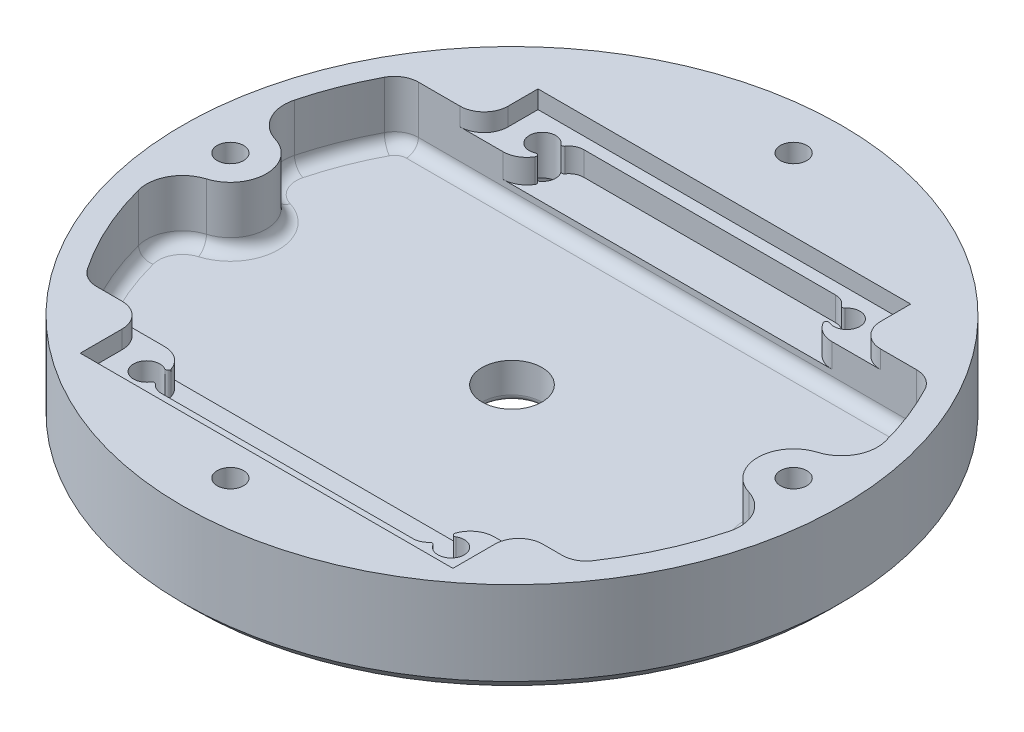
SolidWorks part; units mm, degrees
ref_plane "Спереди" through (0, 0, 0) normal (0, 0, 1) x (1, 0, 0)
ref_plane "Сверху" through (0, 0, 0) normal (0, 1, 0) x (1, 0, 0)
ref_plane "Справа" through (0, 0, 0) normal (1, 0, 0) x (0, 0, -1)
sketch "Эскиз1" plane through (0, 0, 0) normal (0, 1, 0) x (1, 0, 0)
  circle A0 centre (0, 0) radius 27.5
  dimension "D1" = 55
extrude "Бобышка-Вытянуть1" add sketch "Эскиз1" against normal blind 3
sketch "Эскиз2" plane through (0, 0, 0) normal (0, 1, 0) x (1, 0, 0)
  circle A0 centre (0, 0) radius 27.5
  circle A1 centre (0, 0) radius 25.5
  circle A2 centre (0, 0) radius 27.5 construction
  dimension "D1" = 2
extrude "Бобышка-Вытянуть2" add sketch "Эскиз2" along normal blind 5
sketch "Эскиз3" plane through (0, 0, 0) normal (0, 1, 0) x (1, 0, 0)
  line L0 (-21.9552, 12.97) -> (21.9552, 12.97)
  line L1 (15.05, -20.23) -> (-15.05, -20.23) construction
  line L2 (15.05, -20.23) -> (15.05, 16.97) construction
  line L3 (15.05, 16.97) -> (-15.05, 16.97) construction
  line L4 (-15.05, -20.23) -> (-15.05, 16.97) construction
  line L5 (15.05, -20.23) -> (-15.05, 16.97) construction
  line L6 (15.05, 16.97) -> (-15.05, -20.23) construction
  line L7 (-20.4523, -15.23) -> (20.4523, -15.23)
  circle A1 centre (0, 0) radius 25.5
  circle A2 centre (0, 0) radius 25.5 construction
  point P0 (0, -1.63)
  circle M5 centre (0, 0) radius 25.5
  dimension "D1" = 20.23
  dimension "D2" = 37.2
  dimension "D3" = 30.1
  dimension "D4" = 4
  dimension "D5" = 5
extrude "Бобышка-Вытянуть3" add sketch "Эскиз3" along normal up to surface (5 mm away) contours L0 M5 | L7 M5 region at (0, 0, -18.1053) region at (0, 0, 19.4183) up to face at (0, 5, 27.5)
sketch "Эскиз6" plane through (0, 5, 0) normal (0, 1, 0) x (1, 0, 0)
  line L1 (-15.3, 17.47) -> (15.8, 17.47)
  line L2 (-15.3, 17.47) -> (-15.3, -20.73)
  line L3 (-15.3, -20.73) -> (15.8, -20.73)
  line L4 (15.8, 17.47) -> (15.8, -20.73)
  line L5 (-15.3, 17.47) -> (15.8, -20.73) construction
  line L6 (-15.3, -20.73) -> (15.8, 17.47) construction
  point P0 (0.25, -1.63)
  dimension "D1" = 20.73
  dimension "D2" = 31.1
  dimension "D3" = 38.2
  dimension "D4" = 0.25
extrude "Вырез-Вытянуть1" cut sketch "Эскиз6" against normal blind 1.5
sketch "Эскиз7" plane through (0, 3.5, 0) normal (0, 1, 0) x (1, 0, 0)
  line L0 (-10.5, 15.24) -> (10.5, 15.24) construction
  line L1 (-10.5, 16.49) -> (10.5, 16.49)
  line L2 (-10.5, 13.99) -> (10.5, 13.99)
  line L4 (0, 0) -> (0, 15.24) construction
  line L5 (0, 12.97) -> (0, -15.23) construction
  line L6 (0, 17.47) -> (0, 12.97) construction
  line L7 (-20.4523, -15.23) -> (20.4523, -15.23) construction
  line L8 (-10.25, -1.13) -> (10.25, -1.13) construction
  line L9 (-15.3, 12.97) -> (15.8, 12.97) construction
  line L12 (15.8, 17.47) -> (-15.3, 17.47) construction
  line L13 (-11.75, 15.24) -> (-11.75, 12.97)
  line L14 (-21.9552, 12.97) -> (21.9552, 12.97) construction
  line L15 (-11.75, 12.97) -> (11.75, 12.97)
  line L16 (11.75, 12.97) -> (11.75, 15.24)
  line L17 (11.75, -15.23) -> (11.75, -17.5)
  line L18 (-10.5, -17.5) -> (10.5, -17.5) construction
  line L19 (-10.5, -18.75) -> (10.5, -18.75)
  line L20 (-10.5, -16.25) -> (10.5, -16.25)
  line L21 (-11.75, -17.5) -> (-11.75, -15.23)
  line L22 (-11.75, -15.23) -> (11.75, -15.23)
  arc A0 (-10.5, 16.49) -> (-10.5, 13.99) centre (-10.5, 15.24) ccw
  arc A1 (10.5, 13.99) -> (10.5, 16.49) centre (10.5, 15.24) ccw
  arc A2 (-10.5, -18.75) -> (-10.5, -16.25) centre (-10.5, -17.5) cw
  arc A3 (10.5, -16.25) -> (10.5, -18.75) centre (10.5, -17.5) cw
  point P2 (0, 15.24)
  point P13 (0, -1.13)
  point P33 (0, -17.5)
  line M7 (-15.3, 12.97) -> (15.8, 12.97)
  dimension "D1" = 2.5
  dimension "D2" = 23.5
  dimension "D3" = 2.23
extrude "Вырез-Вытянуть2" cut sketch "Эскиз7" against normal blind 2 contours L2 A1 L1 A0 | A1 L2 A0 L13 L16 M7 | L20 A3 L17 L22 L21 A2 | L19 A3 L20 A2 region at (0, 3.5, -15.24) region at (0, 3.5, -13.5015) region at (0, 3.5, 15.7615)
sketch "Эскиз8" plane through (0, 3.5, 0) normal (0, 1, 0) x (1, 0, 0)
  line L0 (0, 0) -> (0, -18.046) construction
  circle A0 centre (-12.7, -17.78) radius 1.1
  circle A1 centre (12.7, -17.78) radius 1.1
  circle A2 centre (-12.7, 15.24) radius 1.1
  circle A3 centre (12.7, 15.24) radius 1.1
  dimension "D3" = 2.2
  dimension "D5" = 2.2
  dimension "D1" = 17.78
  dimension "D2" = 12.7
  dimension "D4" = 15.24
extrude "Вырез-Вытянуть3" cut sketch "Эскиз8" against normal through all
sketch "Эскиз9" plane through (0, 5, 0) normal (0, 1, 0) x (1, 0, 0)
  line L0 (0, 23.5) -> (0, -23.5) construction
  line L1 (-23.5, 3) -> (-25.3229, 3)
  line L2 (-23.5, -3) -> (-25.3229, -3)
  line L3 (23.5, 3) -> (25.3229, 3)
  line L4 (23.5, -3) -> (25.3229, -3)
  circle A0 centre (0, 0) radius 23.5 construction
  arc A1 (-23.5, -3) -> (-23.5, 3) centre (-23.5, 0) ccw
  arc A2 (-21.9552, 12.97) -> (-20.4523, -15.23) centre (0, 0) ccw construction
  arc A3 (-21.9552, 12.97) -> (-20.4523, -15.23) centre (0, 0) ccw construction
  arc A4 (-25.3229, -3) -> (-25.3229, 3) centre (0, 0) cw
  arc A5 (23.5, -3) -> (23.5, 3) centre (23.5, 0) cw
  arc A6 (25.3229, -3) -> (25.3229, 3) centre (0, 0) ccw
  dimension "D1" = 47
  dimension "D2" = 6
extrude "Бобышка-Вытянуть4" add sketch "Эскиз9" against normal through all
sketch "Эскиз10" plane through (0, 5, 0) normal (0, 1, 0) x (1, 0, 0)
  circle A0 centre (0, 0) radius 23.5 construction
  circle A1 centre (0, 23.5) radius 1.1
  circle A2 centre (23.5, 0) radius 1.1
  circle A3 centre (0, -23.5) radius 1.1
  circle A4 centre (-23.5, 0) radius 1.1
  dimension "D1" = 47
  dimension "D2" = 2.2
extrude "Вырез-Вытянуть4" cut sketch "Эскиз10" against normal through all
sketch "Эскиз11" plane through (0, -3, 0) normal (0, -1, 0) x (1, 0, 0)
  line L0 (0, 0) -> (0, 23.5) construction
  line L1 (1.1258, 21.55) -> (2.2517, 23.5) construction
  line L2 (2.2517, 23.5) -> (1.1258, 25.45) construction
  line L3 (1.1258, 25.45) -> (-1.1258, 25.45) construction
  line L4 (-1.1258, 25.45) -> (-2.2517, 23.5) construction
  line L5 (-2.2517, 23.5) -> (-1.1258, 21.55) construction
  line L6 (-1.1258, 21.55) -> (1.1258, 21.55) construction
  line L7 (13.8258, 15.83) -> (14.9517, 17.78)
  line L8 (14.9517, 17.78) -> (13.8258, 19.73)
  line L9 (13.8258, 19.73) -> (11.5742, 19.73)
  line L10 (11.5742, 19.73) -> (10.4483, 17.78)
  line L11 (10.4483, 17.78) -> (11.5742, 15.83)
  line L12 (11.5742, 15.83) -> (13.8258, 15.83)
  line L13 (-11.5742, 15.83) -> (-13.8258, 15.83)
  line L14 (-10.4483, 17.78) -> (-11.5742, 15.83)
  line L15 (-11.5742, 19.73) -> (-10.4483, 17.78)
  line L16 (-13.8258, 19.73) -> (-11.5742, 19.73)
  line L17 (-14.9517, 17.78) -> (-13.8258, 19.73)
  line L18 (-13.8258, 15.83) -> (-14.9517, 17.78)
  line L19 (21.55, -1.1258) -> (23.5, -2.2517) construction
  line L20 (23.5, -2.2517) -> (25.45, -1.1258) construction
  line L21 (25.45, -1.1258) -> (25.45, 1.1258) construction
  line L22 (25.45, 1.1258) -> (23.5, 2.2517) construction
  line L23 (23.5, 2.2517) -> (21.55, 1.1258) construction
  line L24 (21.55, 1.1258) -> (21.55, -1.1258) construction
  line L25 (-1.1258, -21.55) -> (-2.2517, -23.5) construction
  line L26 (-2.2517, -23.5) -> (-1.1258, -25.45) construction
  line L27 (-1.1258, -25.45) -> (1.1258, -25.45) construction
  line L28 (1.1258, -25.45) -> (2.2517, -23.5) construction
  line L29 (2.2517, -23.5) -> (1.1258, -21.55) construction
  line L30 (1.1258, -21.55) -> (-1.1258, -21.55) construction
  line L31 (-21.55, 1.1258) -> (-23.5, 2.2517) construction
  line L32 (-23.5, 2.2517) -> (-25.45, 1.1258) construction
  line L33 (-25.45, 1.1258) -> (-25.45, -1.1258) construction
  line L34 (-25.45, -1.1258) -> (-23.5, -2.2517) construction
  line L35 (-23.5, -2.2517) -> (-21.55, -1.1258) construction
  line L36 (-21.55, -1.1258) -> (-21.55, 1.1258) construction
  line L37 (-12.7, 17.78) -> (-12.7, -15.24) construction
  line L38 (-12.7, 1.27) -> (13.8258, 1.27) construction
  line L39 (11.5742, -13.29) -> (13.8258, -13.29)
  line L40 (10.4483, -15.24) -> (11.5742, -13.29)
  line L41 (11.5742, -17.19) -> (10.4483, -15.24)
  line L42 (13.8258, -17.19) -> (11.5742, -17.19)
  line L43 (14.9517, -15.24) -> (13.8258, -17.19)
  line L44 (13.8258, -13.29) -> (14.9517, -15.24)
  line L45 (-10.4483, -15.24) -> (-11.5742, -13.29)
  line L46 (-11.5742, -17.19) -> (-10.4483, -15.24)
  line L47 (-13.8258, -17.19) -> (-11.5742, -17.19)
  line L48 (-14.9517, -15.24) -> (-13.8258, -17.19)
  line L49 (-13.8258, -13.29) -> (-14.9517, -15.24)
  line L50 (-11.5742, -13.29) -> (-13.8258, -13.29)
  circle A0 centre (0, 23.5) radius 1.95 construction
  circle A1 centre (12.7, 17.78) radius 1.95 construction
  circle A2 centre (-12.7, 17.78) radius 1.95 construction
  circle A3 centre (23.5, 0) radius 1.95 construction
  circle A4 centre (0, -23.5) radius 1.95 construction
  circle A5 centre (-23.5, 0) radius 1.95 construction
  circle A6 centre (23.5, 0) radius 1.1 construction
  circle A7 centre (12.7, -15.24) radius 1.95 construction
  circle A8 centre (-12.7, -15.24) radius 1.95 construction
  point P10 (0, 25.45)
  point P58 (-12.7, 1.27)
  dimension "D1" = 3.9
  dimension "D2" = 3.9
extrude "Вырез-Вытянуть5" cut sketch "Эскиз11" against normal blind 3.2
sketch "Эскиз15" plane through (0, -3, 0) normal (0, -1, 0) x (1, 0, 0)
  line L0 (21.55, -1.1258) -> (23.5, -2.2517)
  line L1 (1.1258, 21.55) -> (2.2517, 23.5)
  line L2 (2.2517, 23.5) -> (1.1258, 25.45)
  line L3 (1.1258, 25.45) -> (-1.1258, 25.45)
  line L4 (-1.1258, 25.45) -> (-2.2517, 23.5)
  line L5 (-2.2517, 23.5) -> (-1.1258, 21.55)
  line L6 (-1.1258, 21.55) -> (1.1258, 21.55)
  line L7 (23.5, -2.2517) -> (25.45, -1.1258)
  line L8 (25.45, -1.1258) -> (25.45, 1.1258)
  line L9 (25.45, 1.1258) -> (23.5, 2.2517)
  line L10 (23.5, 2.2517) -> (21.55, 1.1258)
  line L11 (21.55, 1.1258) -> (21.55, -1.1258)
  line L12 (-1.1258, -21.55) -> (-2.2517, -23.5)
  line L13 (-2.2517, -23.5) -> (-1.1258, -25.45)
  line L14 (-1.1258, -25.45) -> (1.1258, -25.45)
  line L15 (1.1258, -25.45) -> (2.2517, -23.5)
  line L16 (2.2517, -23.5) -> (1.1258, -21.55)
  line L17 (1.1258, -21.55) -> (-1.1258, -21.55)
  line L18 (-21.55, 1.1258) -> (-23.5, 2.2517)
  line L19 (-23.5, 2.2517) -> (-25.45, 1.1258)
  line L20 (-25.45, 1.1258) -> (-25.45, -1.1258)
  line L21 (-25.45, -1.1258) -> (-23.5, -2.2517)
  line L22 (-23.5, -2.2517) -> (-21.55, -1.1258)
  line L23 (-21.55, -1.1258) -> (-21.55, 1.1258)
  circle A0 centre (0, 23.5) radius 1.95 construction
  circle A1 centre (23.5, 0) radius 1.95 construction
  circle A2 centre (0, -23.5) radius 1.95 construction
  circle A3 centre (-23.5, 0) radius 1.95 construction
  circle A4 centre (23.5, 0) radius 1.1 construction
  dimension "D1" = 3.9
extrude "Вырез-Вытянуть7" cut sketch "Эскиз15" against normal blind 3.2
fillet "Скругление1" radius 2 12 edges at (20.4523, 2.5, 15.23) (-20.4523, 2.5, 15.23) (-21.9552, 2.5, -12.97) (21.9552, 2.5, -12.97) (15.8, 4.25, -12.97) (-15.3, 4.25, -12.97) (-11.75, 2.5, -12.97) (11.75, 2.5, -12.97) (-15.3, 4.25, 15.23) (15.8, 4.25, 15.23) (11.75, 2.5, 15.23) (-11.75, 2.5, 15.23)
fillet "Скругление2" radius 3 4 edges at (-25.3229, 2.5, -3) (-25.3229, 2.5, 3) (25.3229, 2.5, 3) (25.3229, 2.5, -3)
chamfer "Фаска1" distance 1 angle 45 1 edges at (0, -3, 27.5)
sketch "Эскиз13" plane through (0, 0, 0) normal (0, 1, 0) x (1, 0, 0)
  circle A0 centre (0, 0) radius 2.5
  dimension "D1" = 5
extrude "Вырез-Вытянуть6" cut sketch "Эскиз13" against normal through all
fillet "Скругление3" radius 0.5 1 edges at (0, -3, 2.5)
fillet "Скругление4" radius 1 16 edges at (23.7574, 0, -9.2649) (24.3752, 0, -4.2791) (20.5, 0, 0) (24.3752, 0, 4.2791) (23.1999, 0, 10.5836) (20.357, 0, 14.998) (0, 0, 15.23) (-20.357, 0, 14.998) (-23.1999, 0, 10.5836) (-24.3752, 0, 4.2791) (-20.5, 0, 0) (-24.3752, 0, -4.2791) (-23.7574, 0, -9.2649) (-21.8151, 0, -12.6828) (0, 0, -12.97) (21.8151, 0, -12.6828)
fillet "Скругление5" radius 0.2 8 edges at (11.75, 2.5, -14.6855) (11.6801, 2.5, -15.6521) (-11.75, 2.5, -14.6855) (-11.6801, 2.5, -15.6521) (11.6299, 2.5, 18.0347) (11.75, 2.5, 17.2255) (-11.6299, 2.5, 18.0347) (-11.75, 2.5, 17.2255)
equation "\"sensor_d\" = 55"
equation "\"sensor_thikness\"= 2"
equation "\"screw_d\"= 2"
equation "\"screw_h1\"= 12"
equation "\"screw_h2\"= 8"
equation "\"screw_hh_d\"= 3.8"
equation "\"screw_hh_h\"= 2"
equation "\"print_offset\"= 0.2"
equation "\"nut_d\"= 3.8"
equation "\"nut_h\"= 2"
equation "\"mounting_r\"= \"sensor_d\" - 8"
equation "\"D1@Эскиз1\"=\"sensor_d\""
equation "\"D1@Бобышка-Вытянуть1\"=3"
equation "\"D1@Эскиз2\" = \"sensor_thikness\""
equation "\"board_size_a\"= 37.2"
equation "\"board_size_b\"= 30.1"
equation "\"mount_hole_a\"= 12.7"
equation "\"mount_hole_b\"= 17.78"
equation "\"D2@Эскиз3\"=\"board_size_a\""
equation "\"D3@Эскиз3\"=\"board_size_b\""
equation "\"D5@Эскиз3\"=5"
equation "\"board_size_c\"= 20.23"
equation "\"D1@Эскиз3\"=\"board_size_c\""
equation "\"D1@Эскиз6\"=\"board_size_c\"+0.5"
equation "\"D2@Эскиз6\"=\"board_size_b\"+1"
equation "\"D3@Эскиз6\"=\"board_size_a\"+1"
equation "\"D1@Вырез-Вытянуть1\"=1.50мм"
equation "\"D1@Эскиз8\"=\"mount_hole_b\""
equation "\"D2@Эскиз8\"=\"mount_hole_a\""
equation "\"D3@Эскиз8\"=\"screw_d\"+\"print_offset\""
equation "\"board_size_d\"= 0.25"
equation "\"D4@Эскиз6\"=\"board_size_d\""
equation "\"D1@Эскиз9\"=\"mounting_r\""
equation "\"D2@Эскиз9\"=\"screw_d\"*3"
equation "\"D1@Эскиз10\"=\"mounting_r\""
equation "\"D2@Эскиз10\"=\"screw_d\"+\"print_offset\""
equation "\"D1@Эскиз11\"=\"nut_d\"+\"print_offset\"/2"
equation "\"D2@Эскиз11\"=\"D1@Эскиз11\""
equation "\"D1@Вырез-Вытянуть5\"=\"nut_h\"+\"print_offset\"+1"
equation "\"D5@Эскиз8\"=\"D3@Эскиз8\""
equation "\"D1@Эскиз15\"=\"nut_d\"+\"print_offset\"/2"
equation "\"D1@Вырез-Вытянуть7\"=\"nut_h\"+\"print_offset\"+1"
